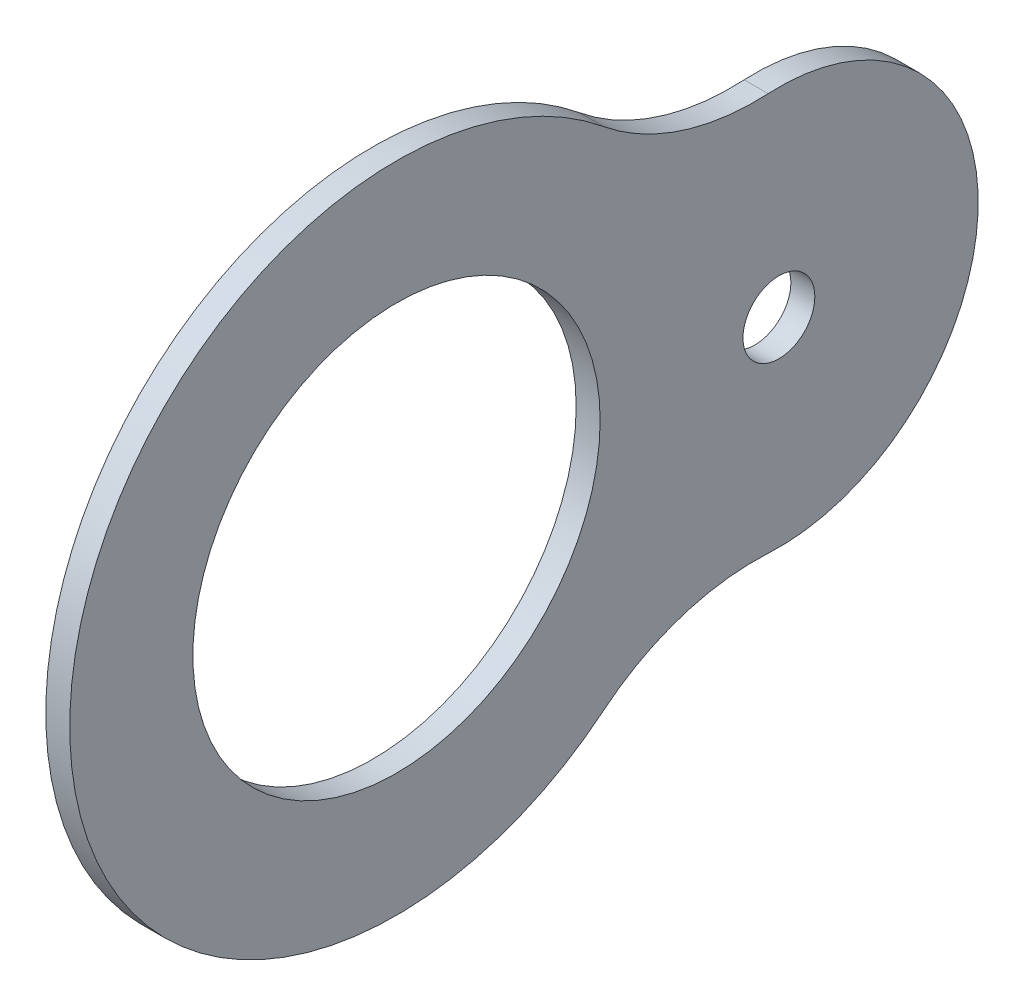
SolidWorks part; units mm, degrees
material "ABS"
ref_plane "Спереди" through (0, 0, 0) normal (0, 0, 1) x (1, 0, 0)
ref_plane "Сверху" through (0, 0, 0) normal (0, 1, 0) x (1, 0, 0)
ref_plane "Справа" through (0, 0, 0) normal (1, 0, 0) x (0, 0, -1)
sketch "Эскиз1" plane through (0, 0, 0) normal (1, 0, 0) x (0, 0, -1)
  circle A0 centre (27.5751, 7.5072) radius 1.5
  circle A1 centre (27.5751, 7.5072) radius 17.965
  circle A2 centre (14.9975, 25.9822) radius 9.385
  circle A3 centre (14.9975, 25.9822) radius 1.5
  circle A4 centre (0, 0) radius 13.64
  circle A5 centre (15.96, 0) radius 8.32
  circle A6 centre (0, 0) radius 8.5
  circle A7 centre (15.96, 0) radius 1.5
  point P6 (15.96, 0)
  point P7 (0, 0)
  dimension "D1" = 3
  dimension "D2" = 35.93
  dimension "D3" = 18.77
  dimension "D5" = 3
  dimension "D10" = 27.28
  dimension "D11" = 16.64
  dimension "D12" = 17
  dimension "D13" = 3
  dimension "D4" = 22.35
  dimension "D6" = 15.96
  dimension "D7" = 30
  dimension "D8" = 26
  dimension "D9" = 13.83
extrude "Бобышка-Вытянуть1" add sketch "Эскиз1" along normal blind 1 contours A5 A1 A4 | A1 A5 A4 | A4 A5 A1 | A5 A4 A1 | A1 A5 A4 A7 | A4 A5 A1 region at (0, -6.5743, -14.4748) region at (0, 0.7203, -18.3825) region at (0, -1.6379, -10.2761) region at (0, 2.3828, -11.9068) region at (0, -1.5118, 13.1817) region at (0, 7.4843, -10.3172)
fillet "Скругление1" radius 10 2 edges at (0.5, -7.1106, -11.64) (0.5, 7.1106, -11.64)
